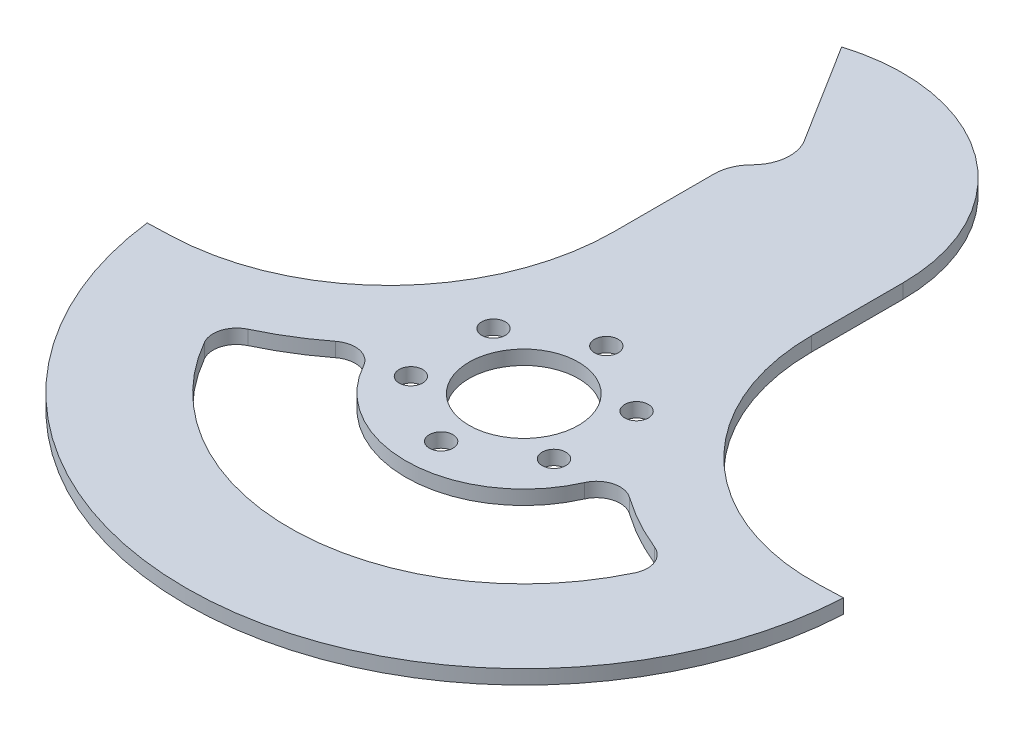
SolidWorks part; units mm, degrees
material "Alloy Steel"
ref_plane "Front Plane" through (0, 0, 0) normal (0, 0, 1) x (1, 0, 0)
ref_plane "Top Plane" through (0, 0, 0) normal (0, 1, 0) x (1, 0, 0)
ref_plane "Right Plane" through (0, 0, 0) normal (1, 0, 0) x (0, 0, -1)
other "Center of Mass"
sketch "Sketch1" plane through (0, 0, 0) normal (0, 1, 0) x (1, 0, 0)
  line L0 (0, 0) -> (-23040.0357, 36803.9862) construction
  line L1 (0, -1000) -> (0, 49000) construction
  line L2 (-29.7853, 97.136) -> (-16.5198, 75.9457)
  line L3 (18.7342, 112.0138) -> (41531.855, 12841.4067) construction
  line L4 (-20, 60.3286) -> (20, 60.3286) construction
  line L5 (-20, 60.3286) -> (-20, 39.1549)
  line L6 (20, 60.3286) -> (20, 40.9875)
  line L7 (0, 0) -> (-71.0663, -8.7258) construction
  line L8 (0, 0) -> (71.5019, -3.7473) construction
  line L9 (-71.0663, -8.7258) -> (71.5019, -3.7473) construction
  line L10 (-71.0663, -8.7258) -> (-66.0694, -8.5513)
  line L11 (71.5019, -3.7473) -> (66.5049, -3.9218)
  line L12 (-28.8426, 54.8122) -> (35326.4965, 35410.1512) construction
  circle A0 centre (0, 0) radius 101.6 construction
  arc A1 (-16.5198, 75.9457) -> (-17.6481, 66.0067) centre (-23.3262, 71.6848) cw
  arc A2 (-17.6481, 66.0067) -> (-20, 60.3286) centre (-11.97, 60.3286) ccw
  arc A3 (-29.7853, 97.136) -> (20, 60.3286) centre (-18.4989, 60.3286) cw
  circle A4 centre (0, 0) radius 71.6 construction
  arc A5 (-71.0663, -8.7258) -> (71.5019, -3.7473) centre (0, 0) ccw
  arc A6 (-66.0694, -8.5513) -> (-20, 39.1549) centre (-67.7353, 39.1549) ccw
  arc A7 (20, 40.9875) -> (66.5049, -3.9218) centre (64.9367, 40.9875) ccw
  circle A8 centre (0, 0) radius 30.5026 construction
  point P9 (0, 60.3286)
  point P20 (0, -71.6)
  point P21 (0, -101.6)
  point P31 (2.4988, -71.5564)
  point P34 (-15.2961, 71.6848)
  dimension "D1" = 203.2
  dimension "D2" = 75
  dimension "D3" = 25
  dimension "D4" = 40
  dimension "D5" = 30
  dimension "D6" = 92
  dimension "D7" = 170
  dimension "D8" = 5
  dimension "D9" = 45
extrude "Boss-Extrude1" add sketch "Sketch1" along normal blind 3.02
sketch "Sketch6" plane through (0, 3.02, 0) normal (0, 1, 0) x (1, 0, 0)
  line L0 (-41.0794, -17.6358) -> (-47.4528, -4.0572) construction
  line L1 (29.2213, -7.1458) -> (38.1596, 4.9002) construction
  arc A0 (-45.5884, -19.5412) -> (46.8909, -16.168) centre (0, 0) ccw
  arc A1 (-16.623, 2.7783) -> (-45.5884, -19.5412) centre (-67.7353, 39.1549) cw
  arc A2 (14.252, 8.9958) -> (46.8909, -16.168) centre (64.9367, 40.9875) ccw
  arc A3 (-16.623, 2.7783) -> (14.252, 8.9958) centre (0, 0) ccw
  arc A4 (-66.0694, -8.5513) -> (-20, 39.1549) centre (-67.7353, 39.1549) ccw construction
  arc A5 (-71.0663, -8.7258) -> (71.5019, -3.7473) centre (0, 0) ccw construction
  arc A6 (20, 40.9875) -> (66.5049, -3.9218) centre (64.9367, 40.9875) ccw construction
  circle A7 centre (0, 0) radius 30.5026 construction
  point P23 (0, -49.6)
  dimension "D1" = 22
  dimension "D2" = 15
extrude "Cut-Extrude2" cut sketch "Sketch6" against normal through all
fillet "Fillet6" radius 5 2 edges at (46.8909, 1.51, 16.168) (-45.5884, 1.51, 19.5412)
sketch "Sketch7" plane through (0, 3.02, 0) normal (0, 1, 0) x (1, 0, 0)
  circle A0 centre (0, 0) radius 25
  dimension "D1" = 50
extrude "Boss-Extrude5" add sketch "Sketch7" against normal up to surface (3.02 mm away) up to face at (0.9289, 0, 19.6333)
fillet "Fillet7" radius 5 2 edges at (24.7558, 1.51, 3.486) (-24.2527, 1.51, 6.0666)
sketch "Sketch8" plane through (0, 3.02, 0) normal (0, 1, 0) x (1, 0, 0)
  circle A0 centre (0.1682, -0.1726) radius 11.6
  dimension "D1" = 23.2
extrude "Cut-Extrude3" cut sketch "Sketch8" against normal through all
sketch "Sketch10" plane through (0, 3.02, 0) normal (0, 1, 0) x (1, 0, 0)
  circle A0 centre (0.1682, -17.6726) radius 7.3266 construction
  circle A1 centre (0, 0) radius 25 construction
  circle A3 centre (0.1682, -17.6726) radius 2.5
  circle A4 centre (-14.9873, -8.9226) radius 2.5
  circle A5 centre (-14.9873, 8.5774) radius 2.5
  circle A6 centre (0.1682, 17.3274) radius 2.5
  circle A7 centre (15.3236, 8.5774) radius 2.5
  circle A8 centre (15.3236, -8.9226) radius 2.5
  point P21 (0.1682, -0.1726)
  dimension "D1" = 5
  dimension "D3" = 35
  dimension "D2" = 6
extrude "Cut-Extrude4" cut sketch "Sketch10" against normal through all
sketch "Sketch11" plane through (0, 0, 0) normal (0, 1, 0) x (1, 0, 0)
  circle A0 centre (0.1682, -0.1726) radius 101.8143 construction
  circle A1 centre (0.1682, -0.1726) radius 11.6 construction
  circle A2 centre (0.1682, -0.1726) radius 71.7461 construction
ref_axis "Axis1" through (0.1682, 0, 0.1726) along (0, 1, 0)
